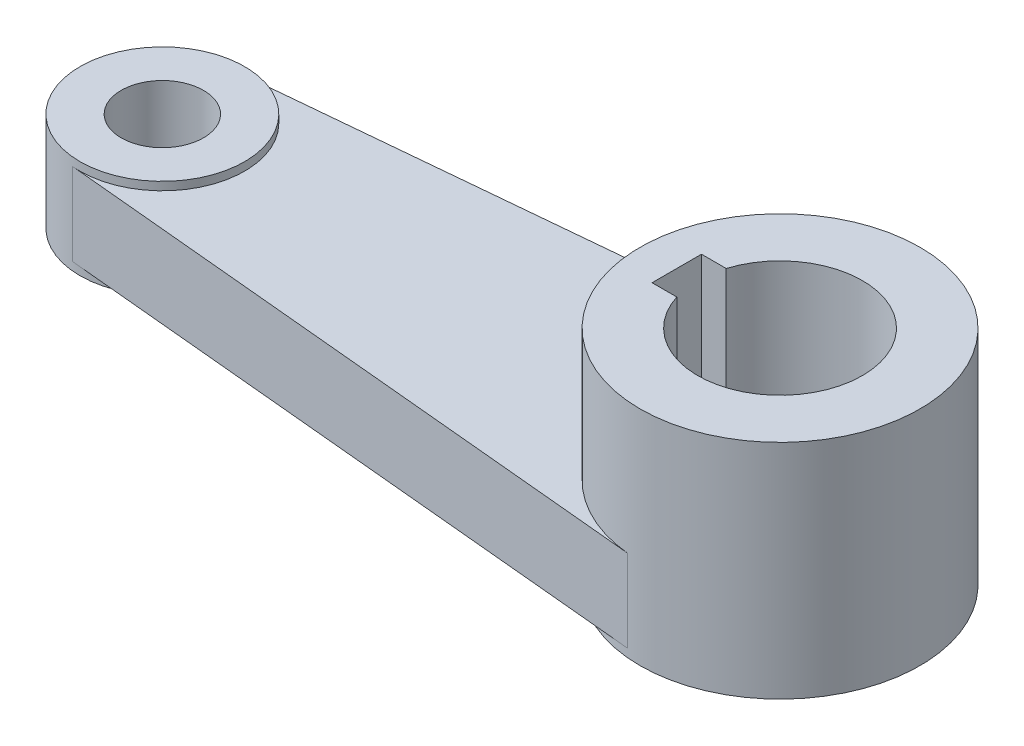
SolidWorks part; units mm, degrees
ref_plane "Piano frontale" through (0, 0, 0) normal (0, 0, 1) x (1, 0, 0)
ref_plane "Piano superiore" through (0, 0, 0) normal (0, 1, 0) x (1, 0, 0)
ref_plane "Piano destro" through (0, 0, 0) normal (1, 0, 0) x (0, 0, -1)
sketch "Schizzo1" plane through (0, 0, 0) normal (0, 1, 0) x (1, 0, 0)
  line L0 (-106.5136, 0) -> (22.563, 0) construction
  line L1 (-12.6288, -3) -> (-15.6288, -3)
  line L2 (-15.6288, -3) -> (-15.6288, 3)
  line L3 (-12.6288, 3) -> (-15.6288, 3)
  line L4 (-79.0227, 9.9563) -> (-4.6761, 16.9258)
  line L5 (-79.0227, -9.9563) -> (-4.6761, -16.9258)
  circle A0 centre (-3.0894, 0) radius 17
  circle A2 centre (-78.0894, 0) radius 10
  circle A3 centre (-78.0894, 0) radius 5
  arc A4 (-12.6288, -3) -> (-12.6288, 3) centre (-3.0894, 0) ccw
  point P9 (0, 0)
  point P10 (-70.2357, 14.6495)
  point P13 (0, 0)
  point P18 (-15.6288, 0)
  point P19 (0, 0)
  point P22 (0, 0)
  dimension "D1" = 34
  dimension "D2" = 20
  dimension "D3" = 20
  dimension "D4" = 10
  dimension "D5" = 6
  dimension "D6" = 3
  dimension "D7" = 75
extrude "Estrusione-Estrusione1" add sketch "Schizzo1" along normal mid plane 12 contours A2 L0 A3 | L0 A2 A3 region at (-78.0894, 0, -5.2236) region at (-70.5894, 0, 0.2236)
extrude "Estrusione-Estrusione2" add sketch "Schizzo1<3>" along normal mid plane 10 contours A2 L0 A0 L4 | L0 A2 L5 A0 region at (-41.9508, 0, -7.1372) region at (-41.9508, 0, 7.1372)
sketch "Schizzo1<3>" plane through (0, 0, 0) normal (0, 1, 0) x (1, 0, 0) same geometry as "Schizzo1"
extrude "Estrusione-Estrusione3" add sketch "Schizzo1<4>" along normal blind 21 and the other way blind 6 contours A0 L0 L2 L3 A4 | L0 A0 A4 L1 L2 region at (-15.3776, 0, -11.1902) region at (-17.8591, 0, 0.3801)
sketch "Schizzo1<4>" plane through (0, 0, 0) normal (0, 1, 0) x (1, 0, 0) same geometry as "Schizzo1"
